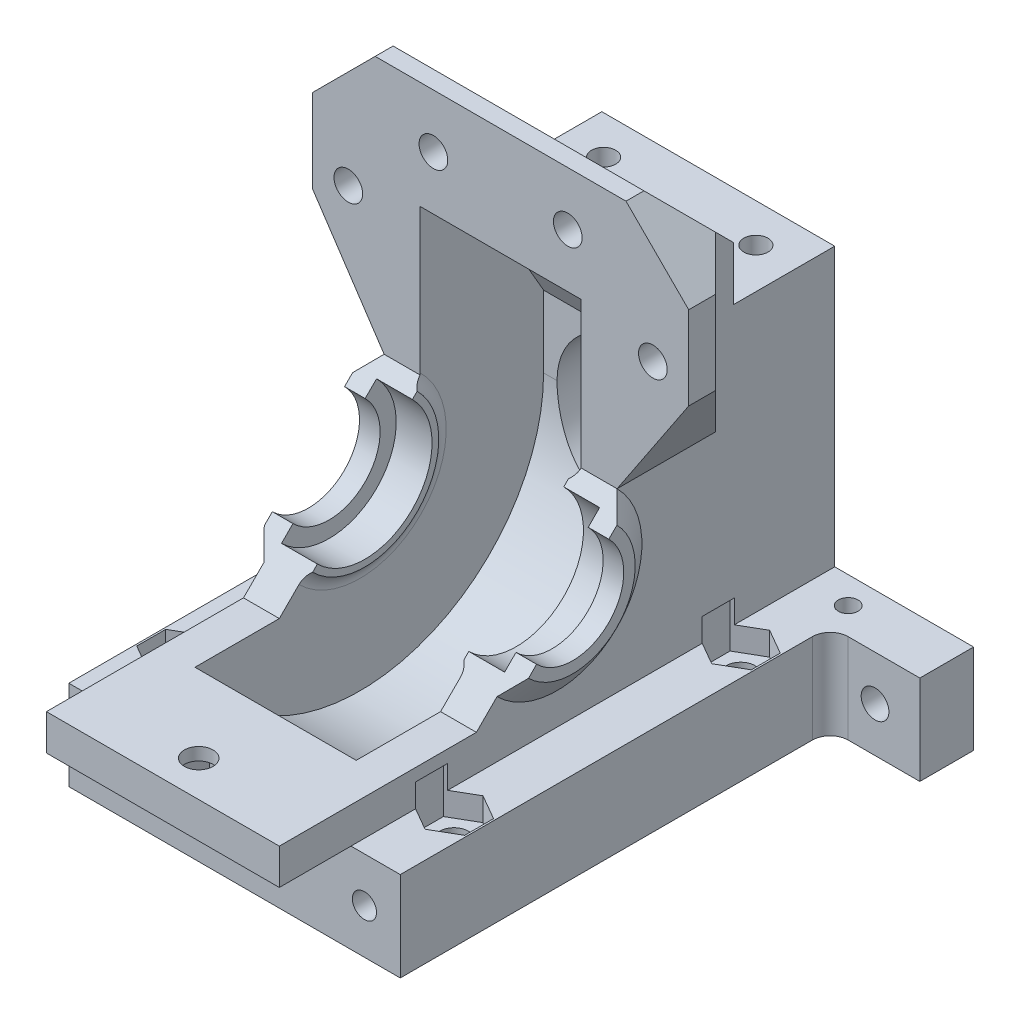
SolidWorks part; units mm, degrees
material "PET"
ref_plane "Plan de face" through (0, 0, 0) normal (0, 0, 1) x (1, 0, 0)
ref_plane "Plan de dessus" through (0, 0, 0) normal (0, 1, 0) x (1, 0, 0)
ref_plane "Plan de droite" through (0, 0, 0) normal (1, 0, 0) x (0, 0, -1)
ref_plane "Plan1" through (0, -23, 0) normal (0, 1, 0) x (1, 0, 0)
sketch "Esquisse1" plane through (0, -23, 0) normal (0, 1, 0) x (1, 0, 0)
  line L0 (0, 36.285) -> (0, -30.3608) construction
  line L1 (18.5, -23) -> (-18.5, -23)
  line L2 (-18.5, -23) -> (-18.5, 25)
  line L3 (-18.5, 25) -> (-28.5, 25)
  line L4 (-28.5, 25) -> (-28.5, 31)
  line L5 (-28.5, 31) -> (28.5, 31)
  line L6 (28.5, 25) -> (28.5, 31)
  line L7 (18.5, 25) -> (28.5, 25)
  line L8 (18.5, -23) -> (18.5, 25)
  circle A0 centre (-17.5, 28) radius 1.1
  circle A1 centre (-15.5, 18) radius 1.6
  circle A2 centre (-15.5, -14) radius 1.6
  circle A3 centre (15.5, -14) radius 1.6
  circle A4 centre (15.5, 18) radius 1.6
  circle A5 centre (17.5, 28) radius 1.1
  point P15 (-28.5, 28)
  point P23 (0, 31)
  point P26 (0, -23)
  dimension "D1" = 3.2
  dimension "D2" = 2.2
  dimension "D3" = 54
  dimension "D4" = 37
  dimension "D5" = 57
  dimension "D6" = 6
  dimension "D7" = 23
  dimension "D8" = 32
  dimension "D9" = 9
  dimension "D10" = 15.5
  dimension "D11" = 17.5
extrude "Boss.-Extru.1" add sketch "Esquisse1" along normal blind 10
sketch "Esquisse2" plane through (0, 0, 0) normal (1, 0, 0) x (0, 0, -1)
  line L0 (31, -13) -> (-31, -13)
  line L1 (-31, -13) -> (-31, -9)
  line L2 (-31, -9) -> (-9, -9)
  line L3 (-9, -9) -> (-4.0305, -4.0305)
  line L4 (6.7, 6.7) -> (6.7, 35)
  line L5 (6.7, 35) -> (8.7, 35)
  line L6 (8.7, 35) -> (19.7, 24)
  line L7 (19.7, 24) -> (19.7, 18)
  line L8 (19.7, 18) -> (31, 18)
  line L9 (31, 18) -> (31, -13)
  line L10 (4.0305, 4.0305) -> (6.7, 6.7)
  line L11 (-23, -23) -> (25, -23) construction
  arc A0 (-4.0305, -4.0305) -> (4.0305, 4.0305) centre (0, 0) ccw
  dimension "D3" = 5.7
  dimension "D1" = 62
  dimension "D2" = 45
  dimension "D4" = 4
  dimension "D5" = 31
  dimension "D6" = 58
  dimension "D7" = 11.3
  dimension "D8" = 2
  dimension "D9" = 45
  dimension "D10" = 6.7
extrude "Boss.-Extru.2" add sketch "Esquisse2" along normal blind 13 and the other way blind 13
ref_axis "Axe1" through (-21.0876, 0, 0) along (1, 0, 0)
sketch "Esquisse3" plane through (13, 0, 0) normal (1, 0, 0) x (0, 0, -1)
  line L0 (-4.0305, -4.0305) -> (-9, -9) construction
  line L1 (-6.7, -6.7) -> (-4.0305, -4.0305)
  line L2 (6.7, 6.7) -> (4.0305, 4.0305)
  arc A0 (6.7, 6.7) -> (-6.7, -6.7) centre (0, 0) cw
  arc A1 (4.0305, 4.0305) -> (-4.0305, -4.0305) centre (0, 0) cw
  arc A2 (-4.0305, -4.0305) -> (4.0305, 4.0305) centre (0, 0) ccw construction
extrude "Boss.-Extru.3" add sketch "Esquisse3" along direction (1, 0, 0) on the side of the normal blind 1.75
sketch "Esquisse4" plane through (19.7, 0, -6.7) normal (0, 0, -1) x (-1, 0, 0)
  line L1 (6.7, 6.7) -> (-1.3, 18.7)
  line L2 (6.7, 6.7) -> (6.7, 26)
  line L3 (6.7, 26) -> (-1.3, 26)
  line L4 (-1.3, 18.7) -> (-1.3, 26)
  line L5 (19.7, -1.2226) -> (19.7, 36.1601) construction
  line L6 (40.7, 18.7) -> (40.7, 26)
  line L7 (32.7, 26) -> (40.7, 26)
  line L8 (32.7, 6.7) -> (32.7, 26)
  line L9 (32.7, 6.7) -> (40.7, 18.7)
  dimension "D1" = 8
  dimension "D2" = 7.3
  dimension "D3" = 19.3
extrude "Boss.-Extru.7" add sketch "Esquisse4" along normal blind 11
chamfer "Chanfrein2" distance 8 angle 45 2 edges at (-21, 22.35, -17.7) (21, 22.35, -17.7)
sketch "Esquisse6" plane through (0, 0, 23) normal (0, 0, 1) x (1, 0, 0)
  line L0 (-21.0876, 0) -> (21.3474, 0) construction
  line L1 (0, -25.736) -> (0, 38.7997) construction
  line L4 (28.5, -13) -> (28.5, -23) construction
  line L5 (18.5, -13) -> (28.5, -13) construction
  circle A0 centre (17, 21) radius 1.6
  circle A1 centre (7.5, 29) radius 1.6
  circle A2 centre (23.5, -18) radius 1.55
  point P13 (28.5, -18)
  point P16 (23.5, -13)
  dimension "D1" = 3.2
  dimension "D6" = 3.1
  dimension "D2" = 21
  dimension "D3" = 29
  dimension "D4" = 7.5
  dimension "D5" = 17
extrude "Enlèv. mat.-Extru.3" cut sketch "Esquisse6" against normal blind 52
sketch "Esquisse7" plane through (0, 0, -31) normal (0, 0, -1) x (-1, 0, 0)
  line L0 (-21, 18.7) -> (-21, 26) construction
  line L1 (-14.2, 22.6166) -> (-17, 24.2332)
  line L2 (-17, 24.2332) -> (-19.8, 22.6166)
  line L3 (-19.8, 22.6166) -> (-19.8, 19.3834)
  line L4 (-19.8, 19.3834) -> (-17, 17.7668)
  line L5 (-17, 17.7668) -> (-14.2, 19.3834)
  line L6 (-14.2, 19.3834) -> (-14.2, 22.6166)
  line L7 (-4.2668, 29) -> (-5.8834, 31.8)
  line L8 (-5.8834, 31.8) -> (-9.1166, 31.8)
  line L9 (-9.1166, 31.8) -> (-10.7332, 29)
  line L10 (-10.7332, 29) -> (-9.1166, 26.2)
  line L11 (-9.1166, 26.2) -> (-5.8834, 26.2)
  line L12 (-5.8834, 26.2) -> (-4.2668, 29)
  line L14 (13, 35) -> (-13, 35) construction
  circle A0 centre (-17, 21) radius 2.8 construction
  circle A1 centre (-7.5, 29) radius 2.8 construction
  dimension "D1" = 5.6
extrude "Enlèv. mat.-Extru.17" cut sketch "Esquisse7" against normal up to vertex (21.3 mm away) up to point (21, 18.7, -9.7)
sketch "Esquisse31" plane through (0, 0, 23) normal (0, 0, 1) x (1, 0, 0)
  line L0 (18.5, -13) -> (18.5, -23) construction
  line L1 (0, -26.7777) -> (0, -12.003) construction
  circle A0 centre (14.5, -18) radius 1.35
  circle A1 centre (-14.5, -18) radius 1.35
  point P7 (18.5, -18)
  dimension "D1" = 2.7
  dimension "D2" = 29
extrude "Enlèv. mat.-Extru.16" cut sketch "Esquisse31" against normal blind 10
sketch "Esquisse9" plane through (0, -13, 0) normal (0, 1, 0) x (1, 0, 0)
  line L1 (18.3, -15.6166) -> (18.3, -12.3834)
  line L2 (18.3, -12.3834) -> (15.5, -10.7668)
  line L3 (15.5, -10.7668) -> (12.7, -12.3834)
  line L4 (12.7, -12.3834) -> (12.7, -15.6166)
  line L5 (12.7, -15.6166) -> (15.5, -17.2332)
  line L6 (15.5, -17.2332) -> (18.3, -15.6166)
  line L7 (18.3, 19.6166) -> (15.5, 21.2332)
  line L8 (15.5, 21.2332) -> (12.7, 19.6166)
  line L9 (12.7, 19.6166) -> (12.7, 16.3834)
  line L10 (12.7, 16.3834) -> (15.5, 14.7668)
  line L11 (15.5, 14.7668) -> (18.3, 16.3834)
  line L12 (18.3, 16.3834) -> (18.3, 19.6166)
  line L13 (18.5, -23) -> (18.5, 25) construction
  circle A0 centre (15.5, -14) radius 2.8 construction
  circle A1 centre (15.5, 18) radius 2.8 construction
  dimension "D1" = 5.6
extrude "Enlèv. mat.-Extru.5" cut sketch "Esquisse9" against normal blind 2.6 and the other way blind 2.6
sketch "Esquisse13" plane through (0, 18, 0) normal (0, 1, 0) x (1, 0, 0)
  line L0 (-13, 19.7) -> (13, 19.7) construction
  line L2 (0, -31.9) -> (0, 31.9) construction
  circle A0 centre (8.5, 26.7) radius 1.35
  dimension "D1" = 2.7
  dimension "D2" = 8.5
  dimension "D3" = 7
extrude "Enlèv. mat.-Extru.6" cut sketch "Esquisse13" against normal blind 8
sketch "Esquisse14" plane through (0, 0, 0) normal (1, 0, 0) x (0, 0, -1)
  line L0 (-9, -9) -> (-31, -9) construction
  line L1 (20.5, 0) -> (20.5, 8)
  line L2 (20.5, 8) -> (13.5718, 20)
  line L3 (13.5718, 20) -> (6.7, 23)
  line L4 (6.7, 35) -> (6.7, 26) construction
  line L5 (-4.0305, -4.0305) -> (-9, -9) construction
  line L7 (-9, -9) -> (-18.4187, -9)
  line L8 (-4.0305, -4.0305) -> (-9, -9)
  line L9 (6.7, 6.7) -> (4.0305, 4.0305)
  line L10 (6.7, 23) -> (6.7, 6.7)
  arc A0 (20.5, 0) -> (-18.4187, -9) centre (0, 0) cw
  arc A1 (-4.0305, -4.0305) -> (4.0305, 4.0305) centre (0, 0) ccw construction
  arc A2 (-4.0305, -4.0305) -> (4.0305, 4.0305) centre (0, 0) ccw
  dimension "D1" = 20.5
  dimension "D2" = 8
  dimension "D3" = 12
  dimension "D4" = 150
  dimension "D5" = 23
extrude "Enlèv. mat.-Extru.7" cut sketch "Esquisse14" against normal blind 9 and the other way blind 9
ref_plane "Plan3" through (8.45, 0, 0) normal (1, 0, 0) x (0, 0, -1)
sketch "Esquisse17" plane through (8.45, 0, 0) normal (1, 0, 0) x (0, 0, -1)
  line L0 (-4.0305, -4.0305) -> (-9, -9) construction
  line L1 (4.0305, 4.0305) -> (5.8336, 5.8336)
  line L2 (-4.0305, -4.0305) -> (-5.8336, -5.8336)
  arc A0 (5.8336, 5.8336) -> (-5.8336, -5.8336) centre (0, 0) cw
  arc A2 (4.0305, 4.0305) -> (-4.0305, -4.0305) centre (0, 0) cw
  dimension "D1" = 2.55
extrude "Boss.-Extru.5" add sketch "Esquisse17" along normal up to next
sketch "Esquisse18" plane through (8.45, 0, 0) normal (-1, 0, 0) x (0, 0, 1)
  line L0 (-5.8336, 5.8336) -> (-4.0305, 4.0305) construction
  line L1 (-5.3033, 5.3033) -> (5.3033, -5.3033)
  arc A0 (-5.3033, 5.3033) -> (5.3033, -5.3033) centre (0, 0) ccw
  dimension "D1" = 7.5
extrude "Enlèv. mat.-Extru.8" cut sketch "Esquisse18" against normal blind 4
mirror "Symétrie1" about plane through (0, 0, 0) normal (1, 0, 0) of "Enlèv. mat.-Extru.16", "Enlèv. mat.-Extru.8", "Enlèv. mat.-Extru.6", "Enlèv. mat.-Extru.5", "Enlèv. mat.-Extru.3", "Boss.-Extru.3", "Boss.-Extru.5", "Enlèv. mat.-Extru.17"
fillet "Congé1" radius 2 4 edges at (9, -5.8336, -5.8336) (-9, -5.8336, -5.8336) (18.5, -18, -25) (-18.5, -18, -25)
sketch "Esquisse21" plane through (0, -13, 0) normal (0, -1, 0) x (1, 0, 0)
  line L0 (0, -31.9) -> (0, 31.9) construction
  circle A0 centre (0, 27) radius 1.6
  dimension "D1" = 3.2
extrude "Enlèv. mat.-Extru.10" cut sketch "Esquisse21" against normal up to next
sketch "Esquisse22" plane through (0, -13, 0) normal (0, -1, 0) x (1, 0, 0)
  line L0 (-13, 31) -> (13, 31) construction
  line L1 (3.2332, 27) -> (1.6166, 29.8)
  line L2 (1.6166, 29.8) -> (-1.6166, 29.8)
  line L3 (-1.6166, 29.8) -> (-3.2332, 27)
  line L4 (-3.2332, 27) -> (-1.6166, 24.2)
  line L5 (-1.6166, 24.2) -> (1.6166, 24.2)
  line L6 (1.6166, 24.2) -> (3.2332, 27)
  circle A0 centre (0, 27) radius 2.8 construction
  dimension "D1" = 5.6
extrude "Enlèv. mat.-Extru.11" cut sketch "Esquisse22" against normal blind 2.6
sketch "Esquisse30" plane through (0, 0, -31) normal (0, 0, -1) x (-1, 0, 0)
  circle A0 centre (0, 0) radius 6
  circle A1 centre (0, 0) radius 3.5
  dimension "D1" = 12
extrude "Boss.-Extru.6" add sketch "Esquisse30" along normal blind 3.5
fillet "Congé2" radius 3.5 1 edges at (6, 0, -31)
sketch "Esquisse25" plane through (0, 0, -31) normal (0, 0, -1) x (-1, 0, 0)
  circle A0 centre (0, 0) radius 5.1
  dimension "D1" = 10.2
extrude "Enlèv. mat.-Extru.12" cut sketch "Esquisse25" against normal up to next and the other way blind 2.5
sketch "Esquisse26" plane through (0, 0, -20.5) normal (0, 0, 1) x (1, 0, 0)
  circle A0 centre (0, 0) radius 7.5
  arc A5 (5.1, 0) -> (-5.1, 0) centre (0, 0) ccw construction
  dimension "D1" = 15
extrude "Enlèv. mat.-Extru.13" cut sketch "Esquisse26" against normal blind 5 and the other way up to next
ref_axis "Axe2" through (0, 0, 13.8458) along (0, 0, -1)
chamfer "Chanfrein3" distance 1.75 distance2 2.5 1 edges at (14.75, -6.7, -6.7) first distance on face at (13.875, -3.35, -3.35)
chamfer "Chanfrein4" distance 2.5 distance2 1.75 1 edges at (-14.75, -6.7, -6.7) first distance on face at (-14.75, -2.6826, -2.6826)
chamfer "Chanfrein5" distance 10 angle 45 2 edges at (13, 26, -12.2) (-13, 26, -12.2)
ref_axis "Axe3" through (8.5, 10, -26.7) along (0, 1, 0)
